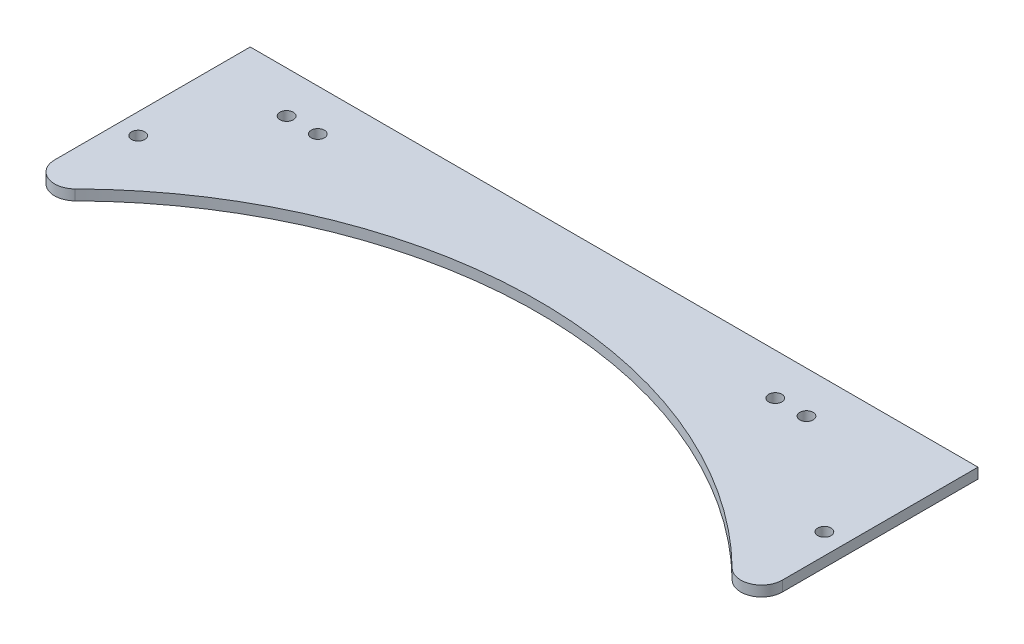
SolidWorks part; units mm, degrees
ref_plane "Front Plane" through (0, 0, 0) normal (0, 0, 1) x (1, 0, 0)
ref_plane "Top Plane" through (0, 0, 0) normal (0, 1, 0) x (1, 0, 0)
ref_plane "Right Plane" through (0, 0, 0) normal (1, 0, 0) x (0, 0, -1)
sketch "Sketch1" plane through (0, 0, 0) normal (0, 1, 0) x (1, 0, 0)
  line L0 (0, 0) -> (0, 76.2)
  line L1 (0, 76.2) -> (222.25, 76.2)
  line L2 (222.25, 76.2) -> (222.25, 0)
  arc A0 (0, 0) -> (222.25, 0) centre (111.125, -89.8026) cw
  circle A1 centre (6.35, 35.639) radius 2.032
  circle A2 centre (215.9, 35.639) radius 2.032
  point P10 (0, 0)
  dimension "D3" = 142.875
  dimension "D4" = 4.064
  dimension "D1" = 76.2
  dimension "D2" = 222.25
  dimension "D5" = 40.561
  dimension "D6" = 6.35
  dimension "D7" = 6.35
extrude "Boss-Extrude1" add sketch "Sketch1" along normal blind 3.175
sketch "Sketch3" plane through (0, 0, 0) normal (0, -1, 0) x (1, 0, 0)
  circle A0 centre (33.3375, -63.5) radius 2.032 construction
  circle A1 centre (23.8125, -63.5) radius 2.032 construction
  circle A2 centre (182.5625, -63.5) radius 2.032 construction
  circle A3 centre (173.0375, -63.5) radius 2.032 construction
  circle A4 centre (33.3375, -63.5) radius 2.032
  circle A5 centre (23.8125, -63.5) radius 2.032
  circle A6 centre (182.5625, -63.5) radius 2.032
  circle A7 centre (173.0375, -63.5) radius 2.032
extrude "Cut-Extrude1" cut sketch "Sketch3" against normal through all
fillet "Fillet1" radius 6.35 2 edges at (0, 1.5875, 0) (222.25, 1.5875, 0)
